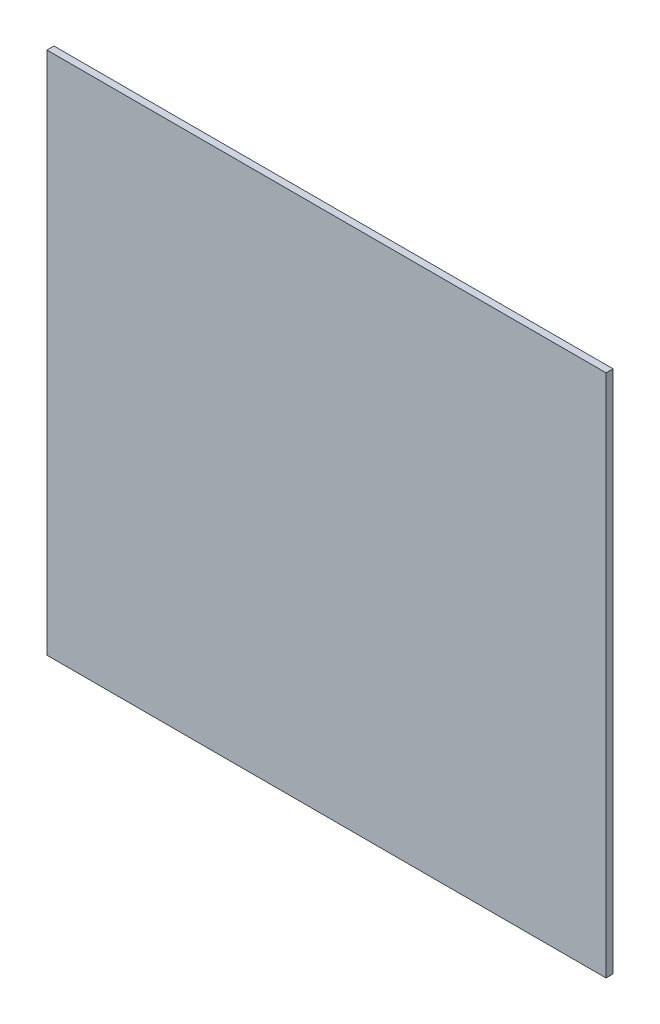
SolidWorks part; units mm, degrees
ref_plane "Спереди" through (0, 0, 0) normal (0, 0, 1) x (1, 0, 0)
ref_plane "Сверху" through (0, 0, 0) normal (0, 1, 0) x (1, 0, 0)
ref_plane "Справа" through (0, 0, 0) normal (1, 0, 0) x (0, 0, -1)
sketch "Эскиз1" plane through (0, 0, 0) normal (0, 0, 1) x (1, 0, 0)
  line L1 (0, 0) -> (800, 0)
  line L2 (0, 0) -> (0, 750)
  line L3 (0, 750) -> (800, 750)
  line L4 (800, 0) -> (800, 750)
  dimension "D1" = 800
  dimension "D2" = 750
extrude "Бобышка-Вытянуть1" add sketch "Эскиз1" along normal blind 10
